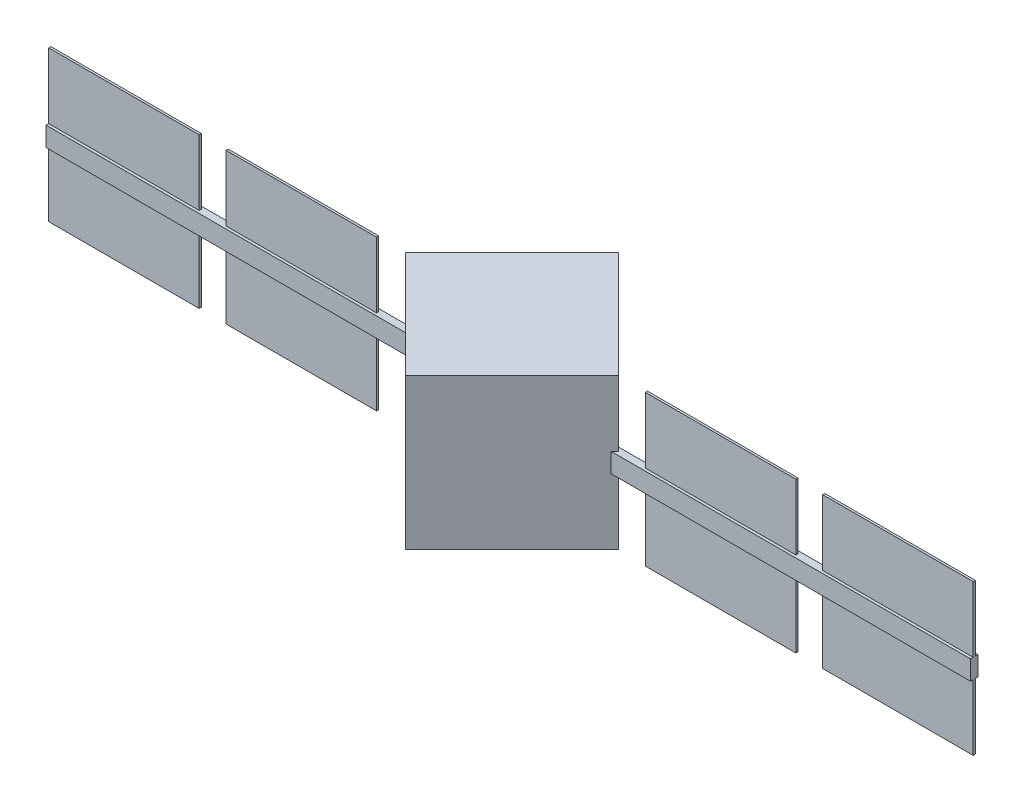
SolidWorks part; units mm, degrees
ref_plane "Piano frontale" through (0, 0, 0) normal (0, 0, 1) x (1, 0, 0)
ref_plane "Piano superiore" through (0, 0, 0) normal (0, 1, 0) x (1, 0, 0)
ref_plane "Piano destro" through (0, 0, 0) normal (1, 0, 0) x (0, 0, -1)
sketch "Schizzo1" plane through (0, 0, 0) normal (0, 1, 0) x (1, 0, 0)
  line L1 (350, -350) -> (-350, -350)
  line L2 (350, -350) -> (350, 350)
  line L3 (350, 350) -> (-350, 350)
  line L4 (-350, -350) -> (-350, 350)
  line L5 (350, -350) -> (-350, 350) construction
  line L6 (350, 350) -> (-350, -350) construction
  point P0 (0, 0)
  dimension "D1" = 700
extrude "Estrusione-Estrusione1" add sketch "Schizzo1" along normal mid plane 700
ref_axis "Asse x" through (-2666.8222, 0, 0) along (1, 0, 0)
ref_axis "Asse y" through (0, 798.5236, 0) along (0, -1, 0)
ref_axis "Asse z" through (0, 0, -1593.2667) along (0, 0, 1)
ref_plane "Piano1" through (0, 0, 0) normal (-0.7071, 0, 0.7071) x (0, -1, 0)
ref_plane "Piano2" through (0, 0, 0) normal (0.7071, 0, 0.7071) x (0, -1, 0)
ref_axis "Assiale" through (1589.8132, 0, -1589.8132) along (-0.7071, 0, 0.7071)
sketch "Schizzo4" plane through (0, 0, 0) normal (-0.7071, 0, 0.7071) x (0, -1, 0)
  line L1 (45, 17.5) -> (-45, 17.5)
  line L2 (45, 17.5) -> (45, -17.5)
  line L3 (45, -17.5) -> (-45, -17.5)
  line L4 (-45, 17.5) -> (-45, -17.5)
  line L5 (45, 17.5) -> (-45, -17.5) construction
  line L6 (45, -17.5) -> (-45, 17.5) construction
  point P0 (0, 0)
  dimension "D1" = 90
  dimension "D2" = 35
extrude "Estrusione-Estrusione2" add sketch "Schizzo4" along normal mid plane 4300
sketch "Schizzo6" plane through (0, 0, 0) normal (0.7071, 0, 0.7071) x (0, -1, 0)
  line L0 (0, 2248.3354) -> (0, -2286.6178) construction
  line L1 (350, -624.9747) -> (-350, -624.9747)
  line L2 (350, -624.9747) -> (350, -1324.9747)
  line L3 (350, -1324.9747) -> (-350, -1324.9747)
  line L4 (-350, -624.9747) -> (-350, -1324.9747)
  line L5 (350, -624.9747) -> (-350, -1324.9747) construction
  line L6 (350, -1324.9747) -> (-350, -624.9747) construction
  line L7 (45, -494.9747) -> (350, -494.9747) construction
  point P0 (0, -974.9747)
  dimension "D1" = 700
  dimension "D2" = 130
extrude "Estrusione-Estrusione3" add sketch "Schizzo6" along normal mid plane 10
sketch "Schizzo7" plane through (0, 0, 0) normal (0.7071, 0, 0.7071) x (0, -1, 0)
  line L0 (0, 2248.3354) -> (0, -2286.6178) construction
  line L1 (350, -2150) -> (-350, -2150)
  line L2 (350, -2150) -> (350, -1450)
  line L3 (350, -1450) -> (-350, -1450)
  line L4 (-350, -2150) -> (-350, -1450)
  line L5 (350, -2150) -> (-350, -1450) construction
  line L6 (350, -1450) -> (-350, -2150) construction
  line L7 (350, -1324.9747) -> (350, -624.9747) construction
  line L8 (350, -1324.9747) -> (350, -624.9747) construction
  line L9 (45, -2150) -> (-45, -2150) construction
  point P0 (0, -1800)
extrude "Estrusione-Estrusione4" add sketch "Schizzo7" along normal mid plane 10
mirror "Specchia1" about plane through (0, 0, 0) normal (-0.7071, 0, 0.7071) of "Estrusione-Estrusione4", "Estrusione-Estrusione3"
move or copy body "Corpo-Sposta/copia1" bodies to move or copy 105 copy no rotation origin (0, 0, 0) rotation axis (0, -1, 0) rotation angle 45
